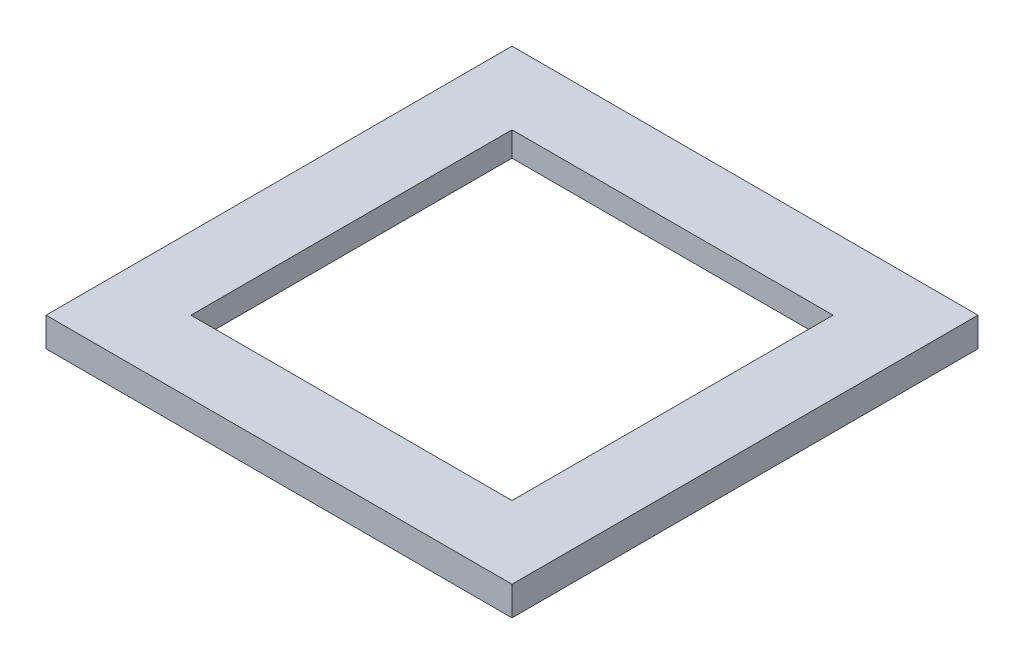
SolidWorks part; units mm, degrees
ref_plane "Front Plane" through (0, 0, 0) normal (0, 0, 1) x (1, 0, 0)
ref_plane "Top Plane" through (0, 0, 0) normal (0, 1, 0) x (1, 0, 0)
ref_plane "Right Plane" through (0, 0, 0) normal (1, 0, 0) x (0, 0, -1)
sketch "Sketch1" plane through (0, 0, 0) normal (0, 1, 0) x (1, 0, 0)
  line L0 (0, 50.8) -> (50.8, 50.8)
  line L5 (0, 50.8) -> (0, 0)
  line L6 (0, 0) -> (50.8, 0)
  line L7 (50.8, 50.8) -> (50.8, 0)
  line L12 (25.4, 42.9) -> (25.4, 50.8) construction
  line L13 (7.9, 42.9) -> (42.9, 42.9)
  line L14 (7.9, 42.9) -> (7.9, 7.9)
  line L15 (7.9, 7.9) -> (42.9, 7.9)
  line L16 (42.9, 42.9) -> (42.9, 7.9)
  line L17 (42.9, 25.4) -> (50.8, 25.4) construction
  point P0 (0, 0)
  point P1 (25.4, 50.8)
  point P2 (50.8, 25.4)
  dimension "D2" = 50.8
  dimension "D4" = 35
extrude "Boss-Extrude1" add sketch "Sketch1" along normal blind 3.175
sketch "Sketch2" plane through (0, 0, 0) normal (0, -1, 0) x (1, 0, 0)
  line L0 (46.0375, -1.5875) -> (4.7625, -1.5875)
  line L1 (1.5875, -4.7625) -> (1.5875, -46.0375)
  line L2 (4.7625, -49.2125) -> (46.0375, -49.2125)
  line L3 (49.2125, -46.0375) -> (49.2125, -4.7625)
  line L4 (2.5174, -2.5174) -> (48.2826, -48.2826) construction
  line L5 (42.9, -7.9) -> (7.9, -42.9) construction
  arc A0 (4.7625, -1.5875) -> (1.5875, -4.7625) centre (4.7625, -4.7625) ccw
  arc A1 (1.5875, -46.0375) -> (4.7625, -49.2125) centre (4.7625, -46.0375) ccw
  arc A2 (46.0375, -49.2125) -> (49.2125, -46.0375) centre (46.0375, -46.0375) ccw
  arc A3 (49.2125, -4.7625) -> (46.0375, -1.5875) centre (46.0375, -4.7625) ccw
  point P4 (7.9, -42.9)
  point P14 (25.4, -25.4)
  point P15 (0, 0)
  point P16 (25.4, -25.4)
  point P17 (3.175, 0)
  point P34 (13.4357, -32.1813)
  point P37 (41.4147, -10.0946)
  point P38 (41.3944, -9.88)
  dimension "D3" = 3.175
  dimension "D1" = 47.625
  dimension "D2" = 47.625
extrude "Cut-Extrude1" cut sketch "Sketch2" against normal blind 0.5
